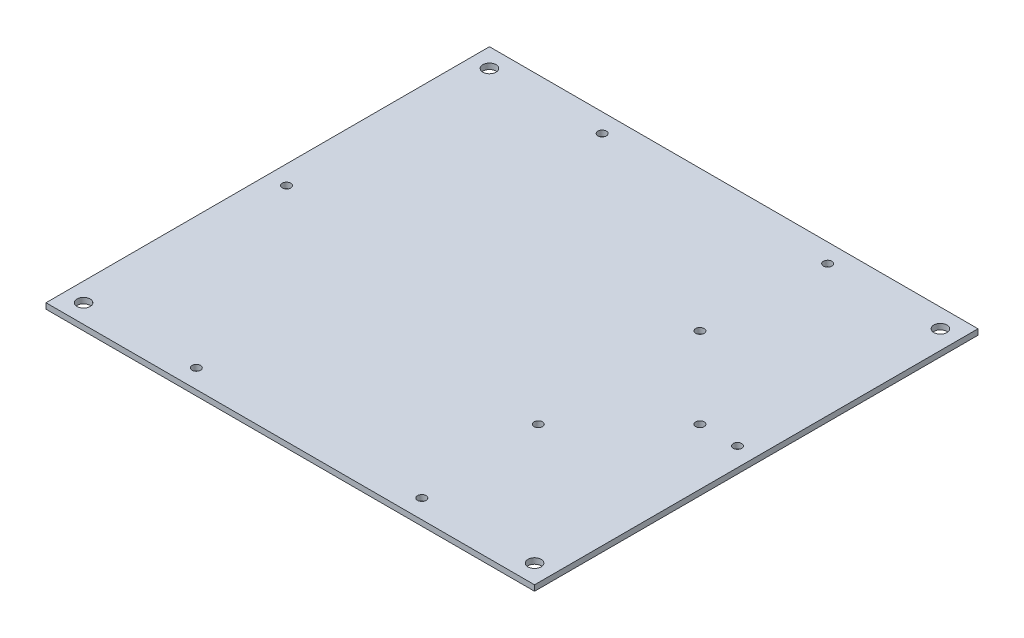
SolidWorks part; units mm, degrees
ref_plane "Спереди" through (0, 0, 0) normal (0, 0, 1) x (1, 0, 0)
ref_plane "Сверху" through (0, 0, 0) normal (0, 1, 0) x (1, 0, 0)
ref_plane "Справа" through (0, 0, 0) normal (1, 0, 0) x (0, 0, -1)
sketch "Эскиз1" plane through (0, 0, 0) normal (0, -1, 0) x (1, 0, 0)
  line L4 (-218.9792, 216.0723) -> (-218.9792, -19.9277)
  line L5 (-218.9792, -19.9277) -> (41.0208, -19.9277)
  line L6 (41.0208, -19.9277) -> (41.0208, 216.0723)
  line L7 (41.0208, 216.0723) -> (-218.9792, 216.0723)
  line L8 (-218.9792, 216.0723) -> (-218.9792, -19.9277)
  line L9 (-218.9792, -19.9277) -> (41.0208, -19.9277)
  line L10 (41.0208, -19.9277) -> (41.0208, 216.0723)
  line L11 (41.0208, 216.0723) -> (-218.9792, 216.0723)
  dimension "D1" = 0
extrude "Бобышка-Вытянуть1" add sketch "Эскиз1" along normal blind 3
sketch "Эскиз2" plane through (0, -3, 0) normal (0, -1, 0) x (1, 0, 0)
  line L0 (-208.9792, -9.9277) -> (31.0208, -9.9277) construction
  line L1 (-208.9792, -9.9277) -> (-208.9792, 206.0723) construction
  line L2 (31.0208, -9.9277) -> (31.0208, 206.0723) construction
  line L3 (-208.9792, 206.0723) -> (31.0208, 206.0723) construction
  circle A0 centre (-208.9792, 98.0723) radius 2.25 construction
  circle A1 centre (-208.9792, 98.0723) radius 2.25
  circle A2 centre (-148.9792, -9.9277) radius 2.25 construction
  circle A3 centre (-148.9792, -9.9277) radius 2.25
  circle A4 centre (-28.9792, -9.9277) radius 2.25 construction
  circle A5 centre (-28.9792, -9.9277) radius 2.25
  circle A6 centre (31.0208, 98.0723) radius 2.25 construction
  circle A7 centre (31.0208, 98.0723) radius 2.25
  circle A8 centre (-28.9792, 206.0723) radius 2.25 construction
  circle A9 centre (-28.9792, 206.0723) radius 2.25
  circle A10 centre (-148.9792, 206.0723) radius 2.25 construction
  circle A11 centre (-148.9792, 206.0723) radius 2.25
  circle A12 centre (-208.9792, -9.9277) radius 3.5
  circle A13 centre (-208.9792, 206.0723) radius 3.5
  circle A14 centre (31.0208, -9.9277) radius 3.5
  circle A15 centre (31.0208, 206.0723) radius 3.5
  dimension "D1" = 7
  dimension "D2" = 7
  dimension "D3" = 7
  dimension "D4" = 7
extrude "Вырез-Вытянуть1" cut sketch "Эскиз2" against normal through all
sketch "Sketch1" plane through (0, 0, 0) normal (0, 1, 0) x (1, 0, 0)
  circle A0 centre (-31.9792, -141.0723) radius 2.25 construction
  circle A1 centre (-31.9792, -141.0723) radius 2.25
  circle A2 centre (11.0208, -98.0723) radius 2.25 construction
  circle A3 centre (11.0208, -98.0723) radius 2.25
  circle A4 centre (-31.9792, -55.0723) radius 2.25 construction
  circle A5 centre (-31.9792, -55.0723) radius 2.25
extrude "Cut-Extrude1" cut sketch "Sketch1" against normal through all
